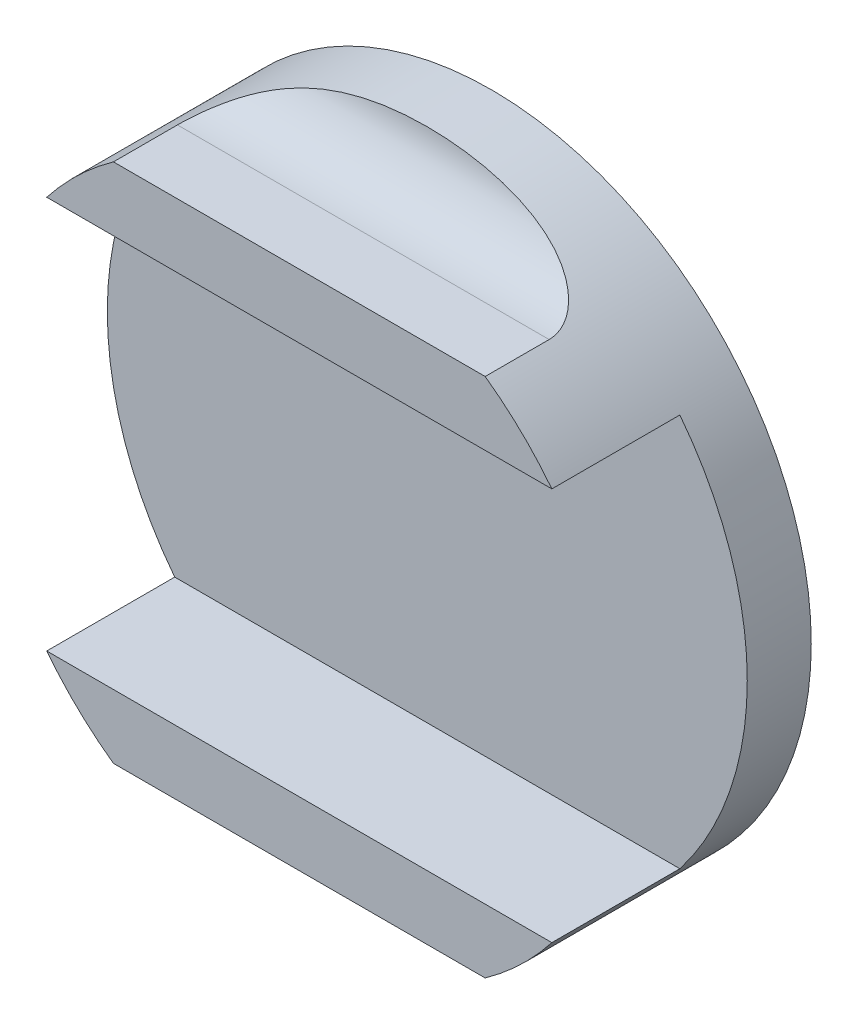
SolidWorks part; units mm, degrees
ref_plane "Plan de face" through (0, 0, 0) normal (0, 0, 1) x (1, 0, 0)
ref_plane "Plan de dessus" through (0, 0, 0) normal (0, 1, 0) x (1, 0, 0)
ref_plane "Plan de droite" through (0, 0, 0) normal (1, 0, 0) x (0, 0, -1)
sketch "Esquisse1" plane through (0, 0, 0) normal (0, 0, 1) x (1, 0, 0)
  circle A0 centre (0, 0) radius 25
  dimension "D1" = 50
extrude "Boss.-Extru.1" add sketch "Esquisse1" along normal blind 5
sketch "Esquisse2" plane through (0, 0, 5) normal (0, 0, 1) x (1, 0, 0)
  line L0 (-25, 0) -> (25, 0) construction
  line L1 (-19.7327, 15.35) -> (19.7327, 15.35)
  line L2 (-14.5216, 20.35) -> (14.5216, 20.35)
  line L3 (-14.5216, -20.35) -> (14.5216, -20.35)
  line L4 (-19.7327, -15.35) -> (19.7327, -15.35)
  circle A0 centre (0, 0) radius 25 construction
  arc A1 (19.7327, 15.35) -> (14.5216, 20.35) centre (0, 0) ccw
  arc A2 (-14.5216, 20.35) -> (-19.7327, 15.35) centre (0, 0) ccw
  arc A3 (-14.5216, -20.35) -> (-19.7327, -15.35) centre (0, 0) cw
  arc A4 (19.7327, -15.35) -> (14.5216, -20.35) centre (0, 0) cw
  dimension "D1" = 15.35
  dimension "D2" = 5
extrude "Boss.-Extru.2" add sketch "Esquisse2" along normal blind 10
fillet "Congé2" radius 5 2 edges at (0, 20.35, 5) (0, -20.35, 5)
